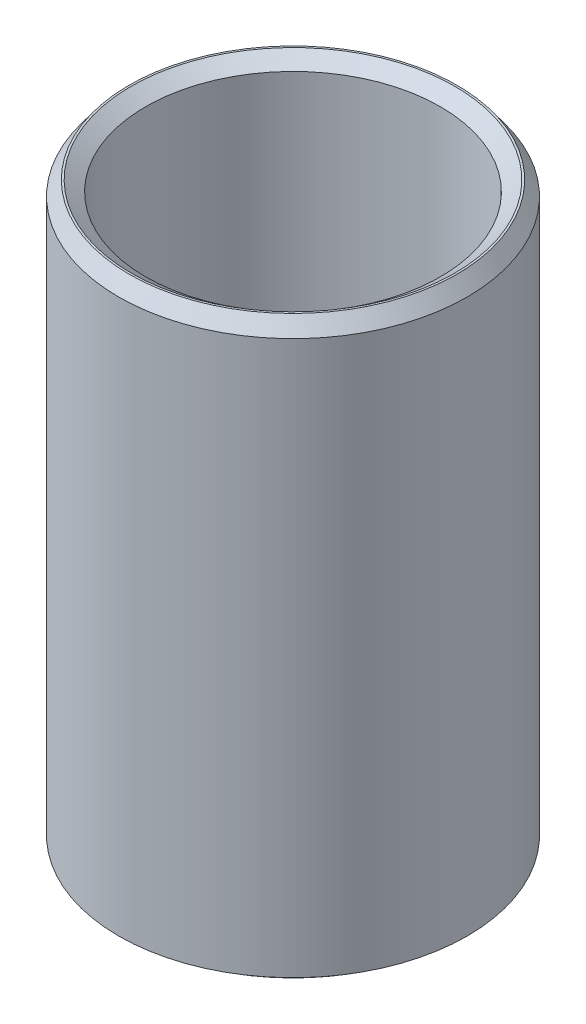
SolidWorks part; units mm, degrees
ref_plane "Front Plane" through (0, 0, 0) normal (0, 0, 1) x (1, 0, 0)
ref_plane "Top Plane" through (0, 0, 0) normal (0, 1, 0) x (1, 0, 0)
ref_plane "Right Plane" through (0, 0, 0) normal (1, 0, 0) x (0, 0, -1)
sketch "Sketch1" plane through (0, 0, 0) normal (0, 1, 0) x (1, 0, 0)
  circle A0 centre (0, 0) radius 27.5
  dimension "SLEEVE_OD" = 55
extrude "Boss-Extrude1" add sketch "Sketch1" along normal blind 91.2519
sketch "Sketch2" plane through (0, 0, 0) normal (0, 1, 0) x (1, 0, 0)
  circle A0 centre (0, 0) radius 23.2566
  dimension "BORE_D" = 46.5131
extrude "Cut-Extrude1" cut sketch "Sketch2" along normal through all
chamfer "Chamfer1" distance 2.2792 angle 35.896 4 edges at (0, 91.2519, 23.2566) (0, 0, 23.2566) (0, 0, 27.5) (0, 91.2519, 27.5) first distance on face at (0, 91.2519, 23.2566) first distance on face at (0, 0, 23.2566) first distance on face at (0, 91.2519, 27.5)
